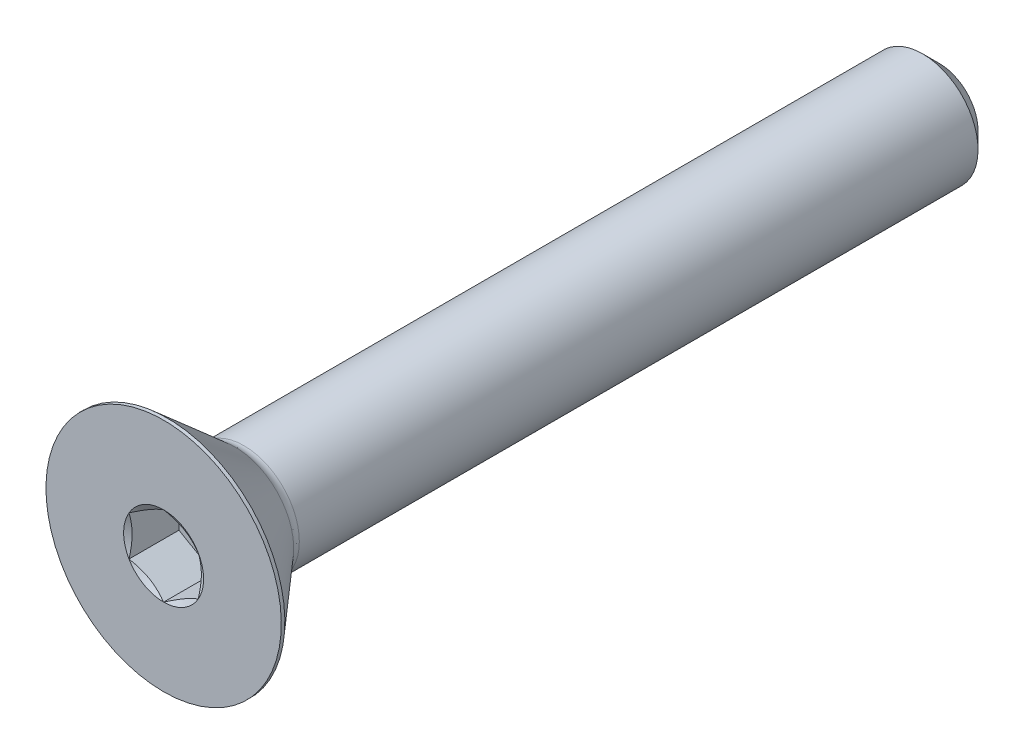
SolidWorks part; units mm, degrees
material "Alloy Steel"
ref_plane "Front" through (0, 0, 0) normal (0, 0, 1) x (1, 0, 0)
ref_plane "Top" through (0, 0, 0) normal (0, 1, 0) x (1, 0, 0)
ref_plane "Right" through (0, 0, 0) normal (1, 0, 0) x (0, 0, -1)
sketch "Sketch1" plane through (0, 0, 0) normal (1, 0, 0) x (0, 0, -1)
  line L0 (0, 6.7437) -> (0.2045, 6.7437) construction
  line L1 (0.2045, 6.7437) -> (4.0894, 3.3666) construction
  line L2 (0, 3.175) -> (44.45, 3.175)
  line L3 (44.45, 3.175) -> (44.45, 0)
  line L4 (44.45, 0) -> (0, 0)
  line L5 (0, 0) -> (0, 6.7437) construction
  line L6 (0, 6.7437) -> (0, -6.7437) construction
  line L7 (44.45, 3.175) -> (44.45, -3.175) construction
  line L8 (0, -6.7437) -> (0.2045, -6.7437) construction
  line L9 (0.2045, -6.7437) -> (4.0894, -3.3666) construction
  line L11 (0, 3.175) -> (0, 0)
  line L12 (4.6018, 3.175) -> (4.6018, 0) construction
  line L13 (22.225, 0) -> (22.225, 3.175) construction
  arc A1 (4.0894, 3.3666) -> (4.6018, 3.175) centre (4.6018, 3.956) ccw construction
  dimension "D1" = 0.2045
  dimension "Min Thread" = 22.225
revolve "Revolve1" add sketch "Sketch1" angle 360 mid plane about L4
sketch "Sketch3" plane through (0, 0, -44.45) normal (0, 0, -1) x (-1, 0, 0)
  circle A0 centre (0, 0) radius 3.175
curve "Helix/Spiral1" pitch 1.27 height 44.45 turns 35
sketch "Sketch2" plane through (0, 0, 0) normal (1, 0, 0) x (0, 0, -1)
  line L0 (44.45, 3.175) -> (45.5613, 3.175)
  line L1 (45.5613, 3.175) -> (45.085, 2.3501)
  line L2 (45.085, 2.3501) -> (44.9263, 2.3501)
  line L3 (44.9263, 2.3501) -> (44.45, 3.175)
  line L4 (44.6881, 2.7626) -> (45.3231, 2.7626) construction
  dimension "D1" = 60
  dimension "D2" = 0.1588
  dimension "D3" = 0.635
ref_plane "Plane2" through (0, 0, -22.225) normal (0, 0, 1) x (1, 0, 0)
chamfer "Chamfer1" distance 0.9525 angle 45 1 edges at (0, 3.175, -44.45)
sweep "Cut-Sweep1" [suppressed] cut profiles "Sketch2" path "Helix/Spiral1"
sketch "Sketch7" plane through (0, 0, 0) normal (1, 0, 0) x (0, 0, -1)
  line L0 (0, 6.7437) -> (0.2045, 6.7437) construction
  line L1 (0.2045, 6.7437) -> (4.0894, 3.3666) construction
  line L2 (0, 6.7437) -> (0.2045, 6.7437)
  line L3 (0.2045, 6.7437) -> (4.0894, 3.3666)
  line L4 (4.6018, 3.175) -> (4.6018, 0) construction
  line L5 (4.6018, 3.175) -> (4.6018, 0)
  line L7 (0, 0) -> (0, 6.7437) construction
  line L8 (0, 0) -> (0, 6.7437)
  line L9 (0, 0) -> (4.6018, 0)
  line L10 (55, 0) -> (-55, 0) construction
  arc A0 (4.0894, 3.3666) -> (4.6018, 3.175) centre (4.6018, 3.956) ccw construction
  arc A1 (4.0894, 3.3666) -> (4.6018, 3.175) centre (4.6018, 3.956) ccw
revolve "Revolve2" add sketch "Sketch7" angle 360 mid plane about L9
ref_plane "Plane1" through (0, 0, -4.6018) normal (0, 0, 1) x (1, 0, 0)
sketch "Sketch8" plane through (0, 0, -4.6018) normal (0, 0, 1) x (1, 0, 0)
  circle A0 centre (0, 0) radius 3.175
extrude "Boss-Extrude1" add sketch "Sketch8" against normal through all draft 46
sketch "Sketch5" plane through (0, 0, 0) normal (0, 0, 1) x (1, 0, 0)
  line L0 (0, 0) -> (-2.2914, 0) construction
  line L1 (0, 0) -> (-2.7496, 1.5875) construction
  line L2 (0, 0) -> (-2.7496, -1.5875) construction
  line L6 (0, 2.2914) -> (0, 1.8898) construction
  line L7 (0, 1.8898) -> (0, 1.4883) construction
  line L9 (0, 2.2914) -> (-1.9844, 1.1457)
  line L10 (-1.9844, 1.1457) -> (-1.9844, -1.1457)
  line L11 (-1.9844, -1.1457) -> (0, -2.2914)
  line L12 (0, -2.2914) -> (1.9844, -1.1457)
  line L13 (1.9844, -1.1457) -> (1.9844, 1.1457)
  line L14 (1.9844, 1.1457) -> (0, 2.2914)
  circle A0 centre (0, 0) radius 2.2914 construction
  circle A1 centre (0, 0) radius 1.8898 construction
  circle A2 centre (0, 0) radius 1.4883 construction
  circle A3 centre (0, 0) radius 1.9844 construction
  dimension "D3" = 2.9766
  dimension "D4" = 30
  dimension "D5" = 30
  dimension "Hex" = 3.9688
extrude "Cut-Extrude2" cut sketch "Sketch5" against normal blind 2.8626
sketch "Sketch6" plane through (0, 0, 0) normal (0, 0, 1) x (1, 0, 0)
  circle A0 centre (0, 0) radius 2.2914
extrude "Cut-Extrude3" cut sketch "Sketch6" against normal blind 2.8626 draft 60
sketch "Sketch9" plane through (0, 0, -4.6018) normal (0, 0, 1) x (1, 0, 0)
  circle A1 centre (0, 0) radius 3.175
  circle A2 centre (0, 0) radius 3.175
  point P0 (0, 3.175)
  dimension "D1" = 0
extrude "Boss-Extrude2" add sketch "Sketch9" against normal up to surface (17.6232 mm away) up to plane "Plane2"
sketch "Sketch10" plane through (0, 0, 0) normal (1, 0, 0) x (0, 0, -1)
  line L0 (44.45, 3.175) -> (44.45, -3.175) construction
  point P0 (42.545, -3.175)
  dimension "D1" = 1.905
equation "\"D3@Helix/Spiral1\" = \"Lg@Sketch1\""
equation "\"D2@Sketch2\" = \"D4@Helix/Spiral1\" * .125"
equation "\"D3@Sketch2\" = \"D4@Helix/Spiral1\" * .5"
equation "\"D1@Chamfer1\" = \"D4@Helix/Spiral1\" * .75"
equation "\"D1@Cut-Extrude2\" = \"Head Ht@Sketch1\" * .7"
equation "\"D1@Sketch1\" = \"Head Ht@Sketch1\" * .05"
equation "\"D1@Sketch10\" = \"D4@Helix/Spiral1\" * 1.5"
equation "\"D1@Cut-Extrude3\" = \"D1@Cut-Extrude2\""
equation "\"D3@Sketch5\" = \"Hex@Sketch5\" * .75"
